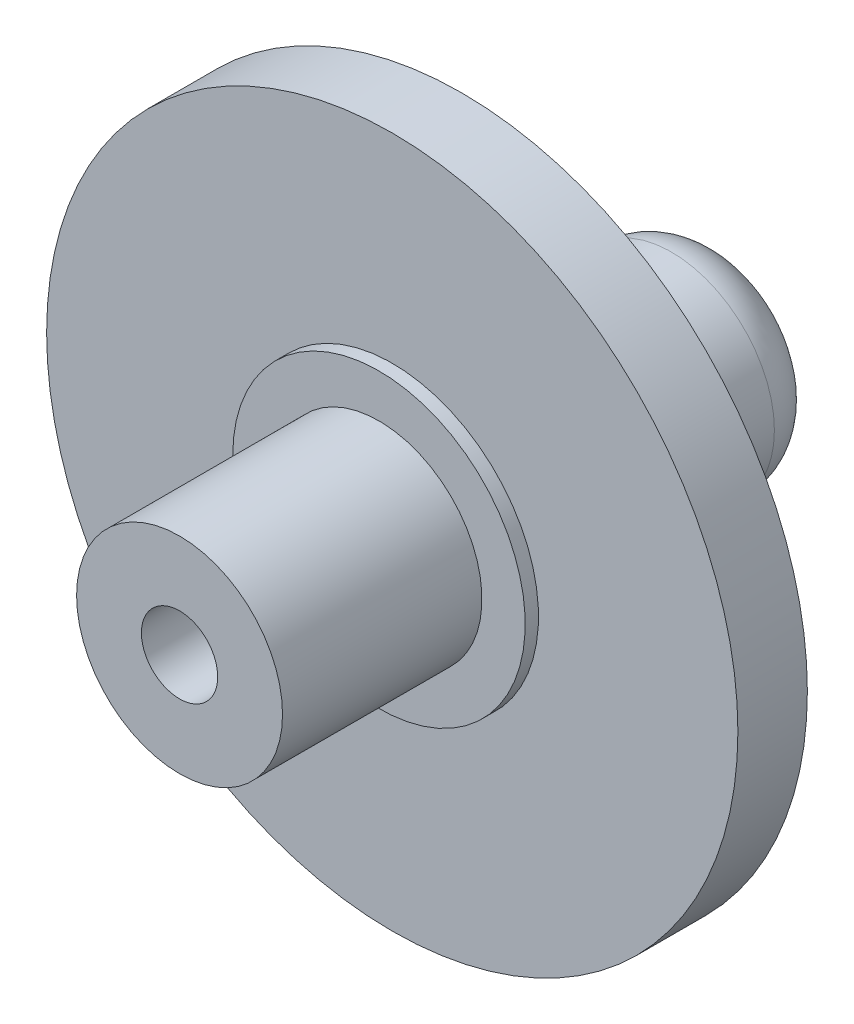
SolidWorks part; units mm, degrees
ref_plane "Front Plane" through (0, 0, 0) normal (0, 0, 1) x (1, 0, 0)
ref_plane "Top Plane" through (0, 0, 0) normal (0, 1, 0) x (1, 0, 0)
ref_plane "Right Plane" through (0, 0, 0) normal (1, 0, 0) x (0, 0, -1)
sketch "Sketch1" plane through (0, 0, 0) normal (0, 0, 1) x (1, 0, 0)
  circle A0 centre (40.4, -23.75) radius 3.873
  circle A1 centre (40.4, -23.75) radius 4 construction
  dimension "D1" = 0.127
extrude "Boss-Extrude1" add sketch "Sketch1" against normal up to surface (7 mm away)
fillet "Fillet1" radius 2 1 edges at (44.273, -23.75, -7)
sketch "Sketch2" plane through (0, 0, 0) normal (0, 0, 1) x (1, 0, 0)
  line L0 (25.4, -31.75) -> (202.0251, -31.75) construction
  circle A0 centre (40.4, -23.75) radius 8
  circle A1 centre (40.4, -23.75) radius 3.873
  circle A2 centre (40.4, -23.75) radius 3.873
  circle M2 centre (40.4, -23.75) radius 3.873
  dimension "D1" = 0
extrude "Boss-Extrude2" add sketch "Sketch2" along normal blind 3 contours A0 M2 | M2 region at (32.6263, -23.75, 0) region at (40.4, -23.75, 0)
sketch "Sketch3" plane through (0, 0, 3) normal (0, 0, 1) x (1, 0, 0)
  circle A0 centre (40.4, -23.75) radius 8 construction
  circle A1 centre (40.4, -23.75) radius 8
  circle A2 centre (40.4, -23.75) radius 13
extrude "Boss-Extrude3" add sketch "Sketch3" along normal offset from surface (2.5 mm away) 0.5 contours A2
chamfer "Chamfer1" distance 3 angle 60 1 edges at (48.4, -23.75, 3) first distance on face at (48.4, -23.75, 3)
sketch "Sketch4" plane through (0, 0, 5.5) normal (0, 0, 1) x (1, 0, 0)
  circle A0 centre (40.4, -23.75) radius 3.873 construction
  circle A1 centre (40.4, -23.75) radius 3.873
  circle A2 centre (40.4, -23.75) radius 5.5
  circle A3 centre (40.4, -23.75) radius 5.5 construction
  circle A4 centre (40.4, -23.75) radius 1.435
extrude "Boss-Extrude4" add sketch "Sketch4" along normal up to surface (8 mm away) contours A1 region at (36.6365, -23.75, 5.5)
extrude "Boss-Extrude5" add sketch "Sketch4<3>" along normal up to surface (0.5 mm away) contours A2 A1 | A1 A4 region at (36.6365, -23.75, 5.5) region at (35.0556, -23.75, 5.5)
sketch "Sketch4<3>" plane through (0, 0, 5.5) normal (0, 0, 1) x (1, 0, 0) same geometry as "Sketch4"
sketch "Sketch6" plane through (0, 0, 5.5) normal (0, 0, 1) x (1, 0, 0)
  circle A1 centre (40.4, -23.75) radius 1.435
  circle A8 centre (40.4, -23.75) radius 1.435
  dimension "D1" = 0
extrude "Cut-Extrude1" cut sketch "Sketch6" against normal through all both and the other way through all
sketch "Sketch5" plane through (0, 0, 13.5) normal (0, 0, 1) x (1, 0, 0)
  circle A1 centre (40.4, -23.75) radius 3.873
  circle A2 centre (40.4, -23.75) radius 3.873
  dimension "D1" = 0
